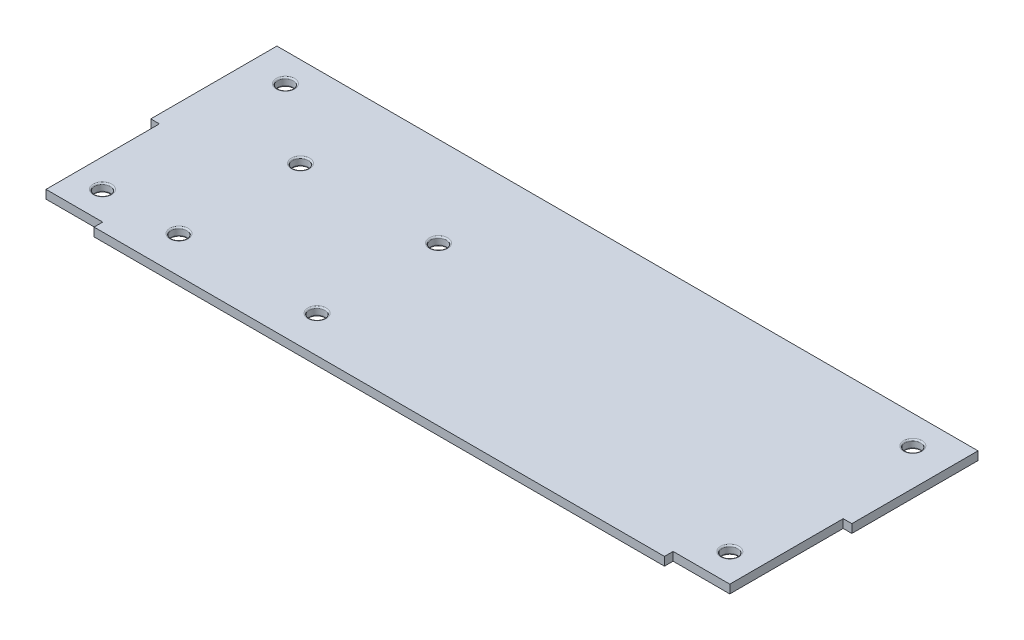
SolidWorks part; units mm, degrees
ref_plane "Front Plane" through (0, 0, 0) normal (0, 0, 1) x (1, 0, 0)
ref_plane "Top Plane" through (0, 0, 0) normal (0, 1, 0) x (1, 0, 0)
ref_plane "Right Plane" through (0, 0, 0) normal (1, 0, 0) x (0, 0, -1)
sketch "Sketch1" plane through (0, 0, 0) normal (0, 1, 0) x (1, 0, 0)
  line L1 (-123.65, -43.775) -> (123.65, -43.775)
  line L2 (-123.65, -43.775) -> (-123.65, 43.775)
  line L3 (-123.65, 43.775) -> (123.65, 43.775)
  line L4 (123.65, -43.775) -> (123.65, 43.775)
  line L5 (-123.65, -43.775) -> (123.65, 43.775) construction
  line L6 (-123.65, 43.775) -> (123.65, -43.775) construction
  point P0 (0, 0)
  dimension "D1" = 247.3
  dimension "D2" = 87.55
extrude "Boss-Extrude1" add sketch "Sketch1" along normal blind 3
sketch "Sketch4" plane through (0, 3, 0) normal (0, 1, 0) x (1, 0, 0)
  line L0 (0, 0) -> (0, -50000) construction
  line L5 (120.6, -40.725) -> (100.6, -43.775) construction
  line L15 (-123.65, -43.775) -> (-120.6, -43.775)
  line L16 (-123.65, -43.775) -> (-123.65, -0.725)
  line L21 (-123.65, -0.725) -> (-120.6, -0.725)
  line L23 (-120.6, -40.725) -> (-120.6, -0.725)
  line L24 (-123.65, -43.775) -> (-120.6, -0.725) construction
  line L25 (-123.65, -0.725) -> (-120.6, -43.775) construction
  line L34 (0, 0) -> (50000, 0) construction
  line L35 (-120.6, -43.775) -> (-100.6, -43.775)
  line L37 (-120.6, -40.725) -> (-100.6, -40.725)
  line L38 (-100.6, -43.775) -> (-100.6, -40.725)
  line L39 (-120.6, -43.775) -> (-100.6, -40.725) construction
  line L40 (-120.6, -40.725) -> (-100.6, -43.775) construction
  line L41 (120.6, -43.775) -> (100.6, -40.725) construction
  line L42 (123.65, -0.725) -> (120.6, -43.775) construction
  line L43 (123.65, -43.775) -> (120.6, -0.725) construction
  line L44 (100.6, -43.775) -> (100.6, -40.725)
  line L45 (120.6, -40.725) -> (100.6, -40.725)
  line L46 (120.6, -43.775) -> (100.6, -43.775)
  line L47 (120.6, -40.725) -> (120.6, -0.725)
  line L48 (123.65, -0.725) -> (120.6, -0.725)
  line L49 (123.65, -43.775) -> (123.65, -0.725)
  line L50 (123.65, -43.775) -> (120.6, -43.775)
  point P4 (-122.125, -22.25)
  point P9 (-110.6, -42.25)
  point P19 (110.6, -42.25)
  point P20 (122.125, -22.25)
  dimension "D1" = 43.05
  dimension "D2" = 3.05
  dimension "D3" = 3.05
  dimension "D4" = 23.05
extrude "Cut-Extrude2" cut sketch "Sketch4" against normal through all
sketch "Sketch2" plane through (0, 3, 0) normal (0, 1, 0) x (1, 0, 0)
  line L0 (0, 0) -> (50000, 0) construction
  line L1 (0, 0) -> (0, 50000) construction
  line L2 (-123.65, 43.775) -> (-123.65, -0.725) construction
  line L3 (123.65, 43.775) -> (-123.65, 43.775) construction
  line L4 (-100.6, -43.775) -> (100.6, -43.775) construction
  circle A0 centre (-110.65, 33.775) radius 2.75
  circle A1 centre (110.65, 33.775) radius 2.75
  circle A4 centre (-110.65, -30.775) radius 2.75
  circle A5 centre (110.65, -30.775) radius 2.75
  dimension "D1" = 5.5
  dimension "D2" = 13
  dimension "D3" = 10
  dimension "D4" = 13
extrude "Cut-Extrude1" cut sketch "Sketch2" against normal through all
fillet "Fillet1" radius 0.5 8 edges at (-110.65, 3, -31.025) (-110.65, 0, -31.025) (110.65, 3, -36.525) (110.65, 0, -36.525) (-110.65, 3, 33.525) (-110.65, 0, 33.525) (110.65, 3, 28.025) (110.65, 0, 28.025)
sketch "Sketch5" plane through (0, 3, 0) normal (0, 1, 0) x (1, 0, 0)
  line L5 (-10, 35.175) -> (10, 35.175)
  line L6 (15.05, 40.225) -> (15.05, 43.775)
  line L8 (-15.05, 43.775) -> (-15.05, 40.225)
  line L9 (-10, 35.225) -> (10, 35.225)
  line L10 (15, 40.225) -> (15, 92.225)
  line L11 (15, 92.225) -> (-15, 92.225)
  line L12 (-15, 92.225) -> (-15, 40.225)
  line L13 (-10, 35.225) -> (10, 35.225) construction
  line L14 (15, 40.225) -> (15, 92.225) construction
  line L15 (15, 92.225) -> (-15, 92.225) construction
  line L16 (-15, 92.225) -> (-15, 40.225) construction
  line L17 (15.05, 92.275) -> (-15.05, 92.275) construction
  line L18 (-15.05, 43.775) -> (15.05, 43.775)
  line L19 (123.65, 43.775) -> (-123.65, 43.775) construction
  line L20 (15.05, 40.225) -> (15.05, 92.275) construction
  line L21 (-15.05, 92.275) -> (-15.05, 40.225) construction
  arc A2 (10, 35.175) -> (15.05, 40.225) centre (10, 40.225) ccw
  arc A3 (-15.05, 40.225) -> (-10, 35.175) centre (-10, 40.225) ccw
  arc A4 (10, 35.225) -> (15, 40.225) centre (10, 40.225) ccw
  arc A5 (-15, 40.225) -> (-10, 35.225) centre (-10, 40.225) ccw
  arc A6 (10, 35.225) -> (15, 40.225) centre (10, 40.225) ccw construction
  arc A7 (-15, 40.225) -> (-10, 35.225) centre (-10, 40.225) ccw construction
  dimension "D1" = 0
  dimension "D2" = 0.05
extrude "Cut-Extrude3" [suppressed] cut sketch "Sketch5" against normal through all
sketch "Sketch6" [suppressed] plane through (0, 3, 0) normal (0, 1, 0) x (1, 0, 0)
  line L0 (-123.65, 92.225) -> (-123.65, -92.225) construction
  line L1 (-123.65, -59.475) -> (-98.57, -59.475)
  line L2 (-123.65, -59.475) -> (-123.65, 4.125)
  line L3 (-123.65, 4.125) -> (-98.57, 4.125)
  line L4 (-95.57, -56.475) -> (-95.57, 1.125)
  line L5 (-123.65, -92.225) -> (123.65, -92.225) construction
  line L6 (0, 0) -> (0, -50000) construction
  line L7 (95.57, -56.475) -> (95.57, 1.125)
  line L8 (123.65, 4.125) -> (98.57, 4.125)
  line L9 (123.65, -59.475) -> (123.65, 4.125)
  line L10 (123.65, -59.475) -> (98.57, -59.475)
  arc A0 (98.57, -59.475) -> (95.57, -56.475) centre (98.57, -56.475) cw
  arc A1 (95.57, 1.125) -> (98.57, 4.125) centre (98.57, 1.125) cw
  arc A2 (-98.57, -59.475) -> (-95.57, -56.475) centre (-98.57, -56.475) ccw
  arc A3 (-95.57, 1.125) -> (-98.57, 4.125) centre (-98.57, 1.125) ccw
  point P17 (95.57, -59.475)
  point P20 (95.57, 4.125)
  point P23 (-95.57, -59.475)
  point P26 (-95.57, 4.125)
  dimension "D4" = 3
  dimension "D1" = 32.75
  dimension "D2" = 63.6
  dimension "D3" = 28.08
extrude "Cut-Extrude4" [suppressed] cut sketch "Sketch6" against normal through all
sketch "Sketch8" [suppressed] plane through (0, 3, 0) normal (0, 1, 0) x (1, 0, 0)
  line L0 (-14.35, -33.2375) -> (-14.35, 49966.7625) construction
  line L1 (53.65, -55.2375) -> (-82.35, -55.2375) construction
  line L2 (53.65, -55.2375) -> (53.65, -11.2375) construction
  line L3 (53.65, -11.2375) -> (-82.35, -11.2375) construction
  line L4 (-82.35, -55.2375) -> (-82.35, -11.2375) construction
  line L5 (53.65, -55.2375) -> (-82.35, -11.2375) construction
  line L6 (53.65, -11.2375) -> (-82.35, -55.2375) construction
  line L7 (-14.35, -33.2375) -> (-50014.35, -33.2375) construction
  circle A0 centre (19.65, -55.2375) radius 1
  circle A1 centre (-14.35, -55.2375) radius 1
  circle A2 centre (-48.35, -55.2375) radius 1
  circle A3 centre (-48.35, -11.2375) radius 1
  circle A4 centre (-14.35, -11.2375) radius 1
  circle A5 centre (19.65, -11.2375) radius 1
  point P4 (-14.35, -33.2375)
  dimension "D1" = 2
  dimension "D3" = 34
extrude "Cut-Extrude6" [suppressed] cut sketch "Sketch8" against normal through all
fillet "Fillet2" [suppressed] radius 0.5
sketch "Sketch9" [suppressed] plane through (0, 3, 0) normal (0, 1, 0) x (1, 0, 0)
  circle A0 centre (-52.194, 74.8945) radius 1.35 construction
  circle A1 centre (5.806, 74.8945) radius 1.35 construction
  circle A2 centre (-74.85, 26.2625) radius 2.75 construction
  circle A3 centre (-52.194, 25.8945) radius 1.35 construction
  circle A4 centre (5.806, 25.8945) radius 1.35 construction
  circle A5 centre (40.15, 26.2625) radius 2.75 construction
  circle A6 centre (-52.194, 74.8945) radius 1.35
  circle A7 centre (5.806, 74.8945) radius 1.35
  circle A8 centre (-74.85, 26.2625) radius 2.75
  circle A9 centre (-52.194, 25.8945) radius 1.35
  circle A10 centre (5.806, 25.8945) radius 1.35
  circle A11 centre (40.15, 26.2625) radius 2.75
extrude "Cut-Extrude7" [suppressed] cut sketch "Sketch9" against normal through all
fillet "Fillet3" [suppressed] radius 0.5
sketch "Sketch10" [suppressed] plane through (0, 3, 0) normal (0, 1, 0) x (1, 0, 0)
  circle A0 centre (74.85, 49.2625) radius 2.75 construction
  circle A1 centre (-40.15, 49.2625) radius 2.75 construction
  circle A2 centre (74.85, 49.2625) radius 2.75
  circle A3 centre (-40.15, 49.2625) radius 2.75
extrude "Cut-Extrude8" [suppressed] cut sketch "Sketch10" against normal through all
fillet "Fillet4" [suppressed] radius 0.5
sketch "Sketch11" plane through (0, 3, 0) normal (0, 1, 0) x (1, 0, 0)
  line L0 (-100.6, -43.775) -> (100.6, -43.775) construction
  line L1 (-123.65, 43.775) -> (-123.65, -0.725) construction
  circle A0 centre (-83.65, -30.775) radius 2.75
  circle A1 centre (-34.9579, -30.775) radius 2.75
  circle A2 centre (-34.9579, 12.0753) radius 2.75
  circle A3 centre (-83.65, 12.0753) radius 2.75
  dimension "D3" = 5.5
  dimension "D1" = 13
  dimension "D2" = 40
extrude "Cut-Extrude9" cut sketch "Sketch11" against normal through all
fillet "Fillet5" radius 0.5 8 edges at (-83.65, 3, 33.525) (-83.65, 0, 33.525) (-34.9579, 3, 33.525) (-34.9579, 0, 33.525) (-34.9579, 3, -9.3253) (-34.9579, 0, -9.3253) (-83.65, 3, -9.3253) (-83.65, 0, -9.3253)
sketch "Sketch12" [suppressed] plane through (0, 0, 0) normal (0, -1, 0) x (1, 0, 0)
  line L0 (0, 0) -> (0, 50000) construction
  line L4 (98.625, -155.4145) -> (122.675, -155.4145)
  line L5 (125.675, -152.4145) -> (125.675, -94.9145)
  line L6 (122.675, -91.9145) -> (98.625, -91.9145)
  line L7 (95.625, -94.9145) -> (95.625, -152.4145)
  line L9 (125.675, -105.2375) -> (125.675, -94.9145) construction
  line L10 (122.675, -91.9145) -> (98.625, -91.9145) construction
  line L11 (95.625, -94.9145) -> (95.625, -105.2375) construction
  line L12 (123.65, -105.2375) -> (-123.65, -105.2375) construction
  line L13 (123.65, -105.2375) -> (-123.65, -105.2375) construction
  line L15 (125.725, -105.2375) -> (125.725, -94.9145)
  line L16 (122.675, -91.8645) -> (98.625, -91.8645)
  line L17 (95.575, -94.9145) -> (95.575, -105.2375)
  line L18 (95.625, -105.2375) -> (125.675, -105.2375) construction
  line L19 (95.575, -105.2875) -> (125.725, -105.2875) construction
  line L20 (95.575, -105.2375) -> (125.725, -105.2375)
  line L21 (125.725, -105.2875) -> (125.725, -94.9145) construction
  line L22 (95.575, -94.9145) -> (95.575, -105.2875) construction
  line L23 (95.625, -152.4145) -> (95.625, -94.9145) construction
  line L24 (-95.625, -94.9145) -> (-95.625, -105.2375) construction
  line L25 (-122.675, -91.9145) -> (-98.625, -91.9145) construction
  line L26 (-125.675, -105.2375) -> (-125.675, -94.9145) construction
  line L27 (-95.575, -105.2375) -> (-125.725, -105.2375)
  line L28 (-95.575, -94.9145) -> (-95.575, -105.2375)
  line L29 (-122.675, -91.8645) -> (-98.625, -91.8645)
  line L30 (-125.725, -105.2375) -> (-125.725, -94.9145)
  arc A0 (125.725, -94.9145) -> (122.675, -91.8645) centre (122.675, -94.9145) ccw
  arc A1 (98.625, -91.8645) -> (95.575, -94.9145) centre (98.625, -94.9145) ccw
  arc A2 (-98.625, -91.9145) -> (-95.625, -94.9145) centre (-98.625, -94.9145) cw construction
  arc A3 (-125.675, -94.9145) -> (-122.675, -91.9145) centre (-122.675, -94.9145) cw construction
  arc A4 (122.675, -155.4145) -> (125.675, -152.4145) centre (122.675, -152.4145) ccw
  arc A5 (125.675, -94.9145) -> (122.675, -91.9145) centre (122.675, -94.9145) ccw
  arc A6 (98.625, -91.9145) -> (95.625, -94.9145) centre (98.625, -94.9145) ccw
  arc A7 (95.625, -152.4145) -> (98.625, -155.4145) centre (98.625, -152.4145) ccw
  arc A9 (125.675, -94.9145) -> (122.675, -91.9145) centre (122.675, -94.9145) ccw construction
  arc A10 (98.625, -91.9145) -> (95.625, -94.9145) centre (98.625, -94.9145) ccw construction
  arc A12 (-98.625, -91.8645) -> (-95.575, -94.9145) centre (-98.625, -94.9145) cw
  arc A13 (-125.725, -94.9145) -> (-122.675, -91.8645) centre (-122.675, -94.9145) cw
  dimension "D1" = 0
  dimension "D2" = 0.05
extrude "Cut-Extrude10" [suppressed] cut sketch "Sketch12" against normal through all
sketch "Sketch13" [suppressed] plane through (0, 0, 0) normal (0, -1, 0) x (1, 0, 0)
  line L0 (122.675, -35.1105) -> (98.625, -35.1105) construction
  line L1 (95.625, -38.1105) -> (95.625, -95.6105) construction
  line L2 (98.625, -98.6105) -> (122.675, -98.6105) construction
  line L3 (125.675, -95.6105) -> (125.675, -38.1105) construction
  line L4 (-98.625, -35.1105) -> (-122.675, -35.1105) construction
  line L5 (-125.675, -38.1105) -> (-125.675, -95.6105) construction
  line L6 (-122.675, -98.6105) -> (-98.625, -98.6105) construction
  line L7 (-95.625, -95.6105) -> (-95.625, -38.1105) construction
  line L8 (122.675, -35.1105) -> (98.625, -35.1105) construction
  line L9 (95.625, -38.1105) -> (95.625, -95.6105) construction
  line L10 (98.625, -98.6105) -> (122.675, -98.6105) construction
  line L11 (125.675, -95.6105) -> (125.675, -38.1105) construction
  line L12 (-98.625, -35.1105) -> (-122.675, -35.1105) construction
  line L13 (-125.675, -38.1105) -> (-125.675, -95.6105) construction
  line L14 (-122.675, -98.6105) -> (-98.625, -98.6105) construction
  line L15 (-95.625, -95.6105) -> (-95.625, -38.1105) construction
  line L16 (122.675, -35.0605) -> (98.625, -35.0605)
  line L17 (95.575, -38.1105) -> (95.575, -95.6105)
  line L18 (98.625, -98.6605) -> (122.675, -98.6605)
  line L19 (125.725, -95.6105) -> (125.725, -38.1105)
  line L20 (-98.625, -35.0605) -> (-122.675, -35.0605)
  line L21 (-125.725, -38.1105) -> (-125.725, -95.6105)
  line L22 (-122.675, -98.6605) -> (-98.625, -98.6605)
  line L23 (-95.575, -95.6105) -> (-95.575, -38.1105)
  arc A0 (98.625, -35.1105) -> (95.625, -38.1105) centre (98.625, -38.1105) ccw construction
  arc A1 (95.625, -95.6105) -> (98.625, -98.6105) centre (98.625, -95.6105) ccw construction
  arc A2 (122.675, -98.6105) -> (125.675, -95.6105) centre (122.675, -95.6105) ccw construction
  arc A3 (125.675, -38.1105) -> (122.675, -35.1105) centre (122.675, -38.1105) ccw construction
  arc A4 (-122.675, -35.1105) -> (-125.675, -38.1105) centre (-122.675, -38.1105) ccw construction
  arc A5 (-125.675, -95.6105) -> (-122.675, -98.6105) centre (-122.675, -95.6105) ccw construction
  arc A6 (-98.625, -98.6105) -> (-95.625, -95.6105) centre (-98.625, -95.6105) ccw construction
  arc A7 (-95.625, -38.1105) -> (-98.625, -35.1105) centre (-98.625, -38.1105) ccw construction
  arc A8 (98.625, -35.1105) -> (95.625, -38.1105) centre (98.625, -38.1105) ccw construction
  arc A9 (95.625, -95.6105) -> (98.625, -98.6105) centre (98.625, -95.6105) ccw construction
  arc A10 (122.675, -98.6105) -> (125.675, -95.6105) centre (122.675, -95.6105) ccw construction
  arc A11 (125.675, -38.1105) -> (122.675, -35.1105) centre (122.675, -38.1105) ccw construction
  arc A12 (-122.675, -35.1105) -> (-125.675, -38.1105) centre (-122.675, -38.1105) ccw construction
  arc A13 (-125.675, -95.6105) -> (-122.675, -98.6105) centre (-122.675, -95.6105) ccw construction
  arc A14 (-98.625, -98.6105) -> (-95.625, -95.6105) centre (-98.625, -95.6105) ccw construction
  arc A15 (-95.625, -38.1105) -> (-98.625, -35.1105) centre (-98.625, -38.1105) ccw construction
  arc A16 (98.625, -35.0605) -> (95.575, -38.1105) centre (98.625, -38.1105) ccw
  arc A17 (95.575, -95.6105) -> (98.625, -98.6605) centre (98.625, -95.6105) ccw
  arc A18 (122.675, -98.6605) -> (125.725, -95.6105) centre (122.675, -95.6105) ccw
  arc A19 (125.725, -38.1105) -> (122.675, -35.0605) centre (122.675, -38.1105) ccw
  arc A20 (-122.675, -35.0605) -> (-125.725, -38.1105) centre (-122.675, -38.1105) ccw
  arc A21 (-125.725, -95.6105) -> (-122.675, -98.6605) centre (-122.675, -95.6105) ccw
  arc A22 (-98.625, -98.6605) -> (-95.575, -95.6105) centre (-98.625, -95.6105) ccw
  arc A23 (-95.575, -38.1105) -> (-98.625, -35.0605) centre (-98.625, -38.1105) ccw
  dimension "D1" = 0.05
extrude "Cut-Extrude11" [suppressed] cut sketch "Sketch13" against normal through all
